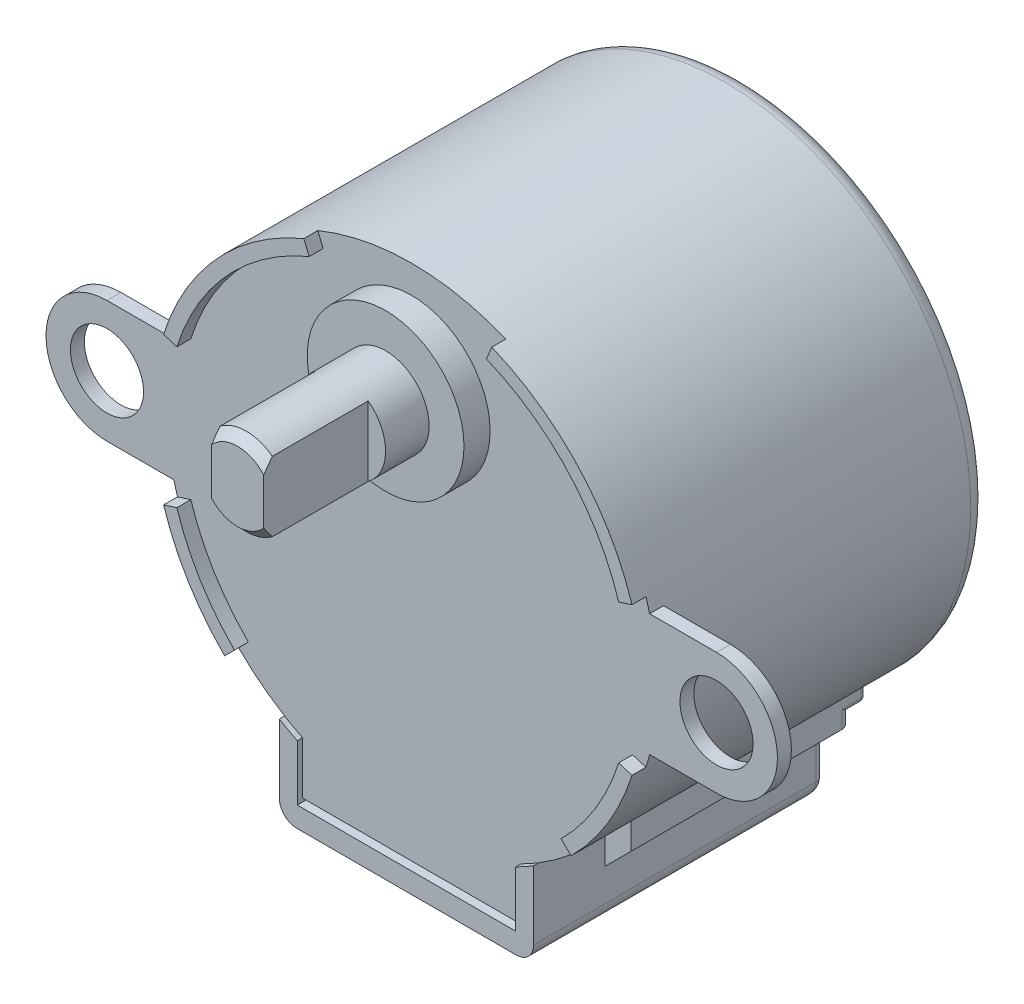
SolidWorks part; units mm, degrees
ref_plane "前视基准面" through (0, 0, 0) normal (0, 0, 1) x (1, 0, 0)
ref_plane "上视基准面" through (0, 0, 0) normal (0, 1, 0) x (1, 0, 0)
ref_plane "右视基准面" through (0, 0, 0) normal (1, 0, 0) x (0, 0, -1)
sketch "草图1" plane through (0, 0, 0) normal (0, 0, 1) x (1, 0, 0)
  circle A0 centre (0, 0) radius 14.1
  dimension "D1" = 28.2
extrude "凸台-拉伸1" add sketch "草图1" along normal blind 19
sketch "草图2" plane through (0, 0, 19) normal (0, 0, 1) x (1, 0, 0)
  line L0 (0, 14.1) -> (0, -14.1) construction
  line L1 (-14.1, 0) -> (14.1, 0) construction
  line L2 (-17.5, 3.5) -> (-13.6587, 3.5)
  line L3 (-17.5, -3.5) -> (-13.6587, -3.5)
  line L4 (17.5, -3.5) -> (13.6587, -3.5)
  line L5 (17.5, 3.5) -> (13.6587, 3.5)
  circle A0 centre (0, 0) radius 14.1 construction
  arc A1 (-17.5, 3.5) -> (-17.5, -3.5) centre (-17.5, 0) ccw
  circle A2 centre (-17.5, 0) radius 2.1
  circle A3 centre (17.5, 0) radius 2.1
  arc A4 (17.5, 3.5) -> (17.5, -3.5) centre (17.5, 0) cw
  arc A5 (-13.6587, 3.5) -> (-13.6587, -3.5) centre (0, 0) ccw
  arc A6 (13.6587, 3.5) -> (13.6587, -3.5) centre (0, 0) cw
  circle M5 centre (0, 0) radius 14.1
  dimension "D1" = 3.5
  dimension "D2" = 4.2
  dimension "D3" = 35
extrude "凸台-拉伸2" add sketch "草图2" against normal blind 0.8 contours L2 A1 L3 A2 M5 | A4 L5 L4 A3 M5 region at (-15.5793, 3.3986, 19) region at (15.5793, 3.3986, 19)
sketch "草图3" plane through (0, 0, 19) normal (0, 0, 1) x (1, 0, 0)
  line L0 (0, 14.1) -> (0, -14.1) construction
  line L1 (21, 0) -> (-21, 0) construction
  arc A0 (13.6587, 3.5) -> (-13.6587, 3.5) centre (0, 0) ccw construction
  arc A1 (-13.6587, -3.5) -> (13.6587, -3.5) centre (0, 0) ccw construction
  arc A2 (17.5, -3.5) -> (17.5, 3.5) centre (17.5, 0) ccw construction
  arc A3 (-17.5, 3.5) -> (-17.5, -3.5) centre (-17.5, 0) ccw construction
  circle A4 centre (0, 8) radius 4.5
  dimension "D1" = 9
  dimension "D2" = 8
extrude "凸台-拉伸3" add sketch "草图3" along normal blind 1.5
sketch "草图4" plane through (0, 0, 20.5) normal (0, 0, 1) x (1, 0, 0)
  circle A0 centre (0, 8) radius 2.5
  dimension "D1" = 5
extrude "凸台-拉伸4" add sketch "草图4" along normal blind 8.5
sketch "草图5" plane through (0, 0, 29) normal (0, 0, 1) x (1, 0, 0)
  line L0 (0, 10.5) -> (0, 5.5) construction
  line L1 (-1.5, 10) -> (-1.5, 6)
  line L2 (1.5, 10) -> (1.5, 6)
  circle A0 centre (0, 8) radius 2.5 construction
  circle A1 centre (0, 8) radius 2.5 construction
  arc A2 (-1.5, 10) -> (-1.5, 6) centre (0, 8) ccw
  arc A3 (1.5, 6) -> (1.5, 10) centre (0, 8) ccw
extrude "切除-拉伸1" cut sketch "草图5" against normal blind 6
chamfer "倒角1" distance 0.5 angle 45 2 edges at (0, 10.5, 29) (0, 5.5, 29)
fillet "圆角1" radius 1 1 edges at (14.1, 0, 0)
sketch "草图6" plane through (0, 0, 19) normal (0, 0, 1) x (1, 0, 0)
  line L0 (0, 14.1) -> (0, -14.1) construction
  line L2 (-6.27, -12.6292) -> (6.27, -12.6292)
  line L3 (-6.27, -12.6292) -> (-6.27, -15.6292)
  line L4 (-6.27, -15.6292) -> (6.27, -15.6292)
  line L5 (6.27, -12.6292) -> (6.27, -15.6292)
  arc A0 (13.6587, 3.5) -> (-13.6587, 3.5) centre (0, 0) ccw construction
  arc A1 (-13.6587, -3.5) -> (13.6587, -3.5) centre (0, 0) ccw construction
  dimension "D1" = 12.54
  dimension "D2" = 3
extrude "凸台-拉伸5" add sketch "草图6" against normal blind 0.8
sketch "草图7" plane through (0, 0, 19) normal (0, 0, 1) x (1, 0, 0)
  line L0 (0, 14.1) -> (0, -15.6292) construction
  line L1 (-6.27, -15.6292) -> (6.27, -15.6292) construction
  line L2 (-7.3, -12.0632) -> (-7.3, -17)
  line L3 (-7.3, -17) -> (7.3, -17)
  line L4 (7.3, -17) -> (7.3, -12.0632)
  line L5 (6.27, -15.6292) -> (6.27, -12.6292) construction
  line L6 (-6.27, -12.6292) -> (-6.27, -15.8292)
  line L7 (-6.27, -15.8292) -> (6.27, -15.8292)
  line L8 (6.27, -15.8292) -> (6.27, -12.6292)
  arc A0 (13.6587, 3.5) -> (-13.6587, 3.5) centre (0, 0) ccw construction
  arc A1 (-13.6587, -3.5) -> (-6.27, -12.6292) centre (0, 0) ccw construction
  arc A2 (6.27, -12.6292) -> (13.6587, -3.5) centre (0, 0) ccw construction
  arc A3 (-7.3, -12.0632) -> (-6.27, -12.6292) centre (0, 0) ccw
  arc A4 (7.3, -12.0632) -> (6.27, -12.6292) centre (0, 0) cw
  dimension "D3" = 0.2
  dimension "D1" = 17
  dimension "D2" = 14.6
extrude "凸台-拉伸6" add sketch "草图7" along normal blind 0.3 and the other way blind 16.4 separate body
sketch "草图8" plane through (0, 0, 2.6) normal (0, 0, -1) x (-1, 0, 0)
  line L0 (0, -17) -> (0, 13.1) construction
  line L1 (7.3, -17) -> (-7.3, -17) construction
  line L2 (-8.8, -12.64) -> (-8.8, -11.0168)
  line L3 (-7.3, -14.14) -> (-7.3, -17)
  line L4 (-8.8, -12.64) -> (-7.3, -14.14)
  line L5 (-7.3, -17) -> (-7.3, -12.0632) construction
  line L6 (-7.3, -17) -> (7.3, -17)
  line L7 (7.3, -14.14) -> (7.3, -17)
  line L8 (8.8, -12.64) -> (7.3, -14.14)
  line L9 (8.8, -12.64) -> (8.8, -11.0168)
  circle A0 centre (0, 0) radius 13.1 construction
  circle A1 centre (0, 0) radius 14.1 construction
  arc A2 (8.8, -11.0168) -> (-8.8, -11.0168) centre (0, 0) cw
  dimension "D1" = 45
  dimension "D2" = 1.5
  dimension "D3" = 2.86
extrude "凸台-拉伸7" add sketch "草图8" against normal blind 12.6
sketch "草图9" plane through (0, 0, 2.6) normal (0, 0, -1) x (-1, 0, 0)
  line L0 (8.8, -12.64) -> (8.8, -11.0168) construction
  line L1 (-8.8, -11.0168) -> (-8.8, -12.64) construction
  line L2 (0, 0) -> (0, -13.1) construction
  line L3 (-1.5, -14.02) -> (-1.5, -14.6233)
  line L4 (-8.8, -11.775) -> (-8.8, -11.0168)
  line L5 (1.5, -14.02) -> (1.5, -14.6233)
  line L6 (8.8, -11.775) -> (8.8, -11.0168)
  arc A0 (8.8, -11.775) -> (-8.8, -11.775) centre (0, 0) cw construction
  arc A1 (-8.8, -11.0168) -> (8.8, -11.0168) centre (0, 0) ccw construction
  circle A2 centre (0, 0) radius 13.1 construction
  arc A3 (-8.8, -11.0168) -> (-1.5, -14.02) centre (0, 0) ccw
  arc A4 (-8.8, -11.775) -> (-1.5, -14.6233) centre (0, 0) ccw
  arc A5 (8.8, -11.775) -> (1.5, -14.6233) centre (0, 0) cw
  arc A6 (8.8, -11.0168) -> (1.5, -14.02) centre (0, 0) cw
  point P24 (1.5, -14.3216)
  dimension "D1" = 0.6
  dimension "D2" = 3
extrude "凸台-拉伸8" add sketch "草图9" along normal blind 0.9
fillet "圆角2" radius 0.5 6 edges at (-8.8, -12.2075, 2.6) (-7.3, -15.57, 2.6) (-8.05, -13.39, 2.6) (8.8, -12.2075, 2.6) (8.05, -13.39, 2.6) (7.3, -15.57, 2.6)
fillet "圆角3" radius 1 5 edges at (-7.3, -17, 11.2) (-7.1536, -17, 2.7464) (7.1536, -17, 2.7464) (7.3, -17, 11.2) (0, -17, 2.6)
fillet "圆角4" radius 0.3 10 edges at (8.8, -11.775, 2.4) (-8.8, -11.775, 2.4) (-1.5, -14.6233, 2.15) (1.5, -14.6233, 2.15) (8.8, -11.3959, 1.7) (5.3433, -13.6945, 1.7) (1.5, -14.3216, 1.7) (-1.5, -14.3216, 1.7) (-8.8, -11.3959, 1.7) (-5.3433, -13.6945, 1.7)
sketch "草图10" plane through (0, 0, 19) normal (0, 0, 1) x (1, 0, 0)
  line L0 (0, 0) -> (0, 14.1) construction
  line L1 (-21, 0) -> (21, 0) construction
  line L2 (-13.4474, 4.24) -> (-12.6844, 3.9994)
  line L3 (-5.3958, 13.0267) -> (0, 0) construction
  line L4 (-5.3958, 13.0267) -> (-5.0897, 12.2876)
  line L5 (13.4474, 4.24) -> (12.6844, 3.9994)
  line L6 (5.3958, 13.0267) -> (5.0897, 12.2876)
  line L7 (5.0897, 12.2876) -> (0, 0) construction
  line L8 (-12.6844, 3.9994) -> (0, 0) construction
  line L9 (0, 0) -> (12.6844, 3.9994) construction
  line L10 (0, 0) -> (-13.4474, -4.24) construction
  line L11 (0, 0) -> (-9.3804, -9.4285) construction
  line L12 (-13.4474, -4.24) -> (-12.6844, -3.9994)
  line L13 (-9.9447, -9.9957) -> (-9.3804, -9.4285)
  line L14 (0, 0) -> (0, -15.6292) construction
  line L15 (-6.27, -15.6292) -> (6.27, -15.6292) construction
  line L16 (9.9447, -9.9957) -> (9.3804, -9.4285)
  line L17 (13.4474, -4.24) -> (12.6844, -3.9994)
  line L18 (0, 0) -> (9.3804, -9.4285) construction
  line L19 (0, 0) -> (13.4474, -4.24) construction
  arc A0 (13.6587, 3.5) -> (-13.6587, 3.5) centre (0, 0) ccw construction
  arc A1 (-17.5, 3.5) -> (-17.5, -3.5) centre (-17.5, 0) ccw construction
  arc A2 (17.5, -3.5) -> (17.5, 3.5) centre (17.5, 0) ccw construction
  arc A3 (-13.4474, 4.24) -> (-5.3958, 13.0267) centre (0, 0) cw
  arc A4 (-5.0897, 12.2876) -> (-12.6844, 3.9994) centre (0, 0) ccw
  arc A5 (5.0897, 12.2876) -> (12.6844, 3.9994) centre (0, 0) cw
  arc A6 (13.4474, 4.24) -> (5.3958, 13.0267) centre (0, 0) ccw
  arc A7 (-13.6587, -3.5) -> (-7.3, -12.0632) centre (0, 0) ccw construction
  arc A8 (-13.4474, -4.24) -> (-9.9447, -9.9957) centre (0, 0) ccw
  arc A9 (-12.6844, -3.9994) -> (-9.3804, -9.4285) centre (0, 0) ccw
  arc A10 (13.4474, -4.24) -> (9.9447, -9.9957) centre (0, 0) cw
  arc A11 (12.6844, -3.9994) -> (9.3804, -9.4285) centre (0, 0) cw
  dimension "D1" = 0.8
  dimension "D4" = 27.646
  dimension "D2" = 45
  dimension "D3" = 145
extrude "凸台-拉伸9" add sketch "草图10" along normal blind 0.8
